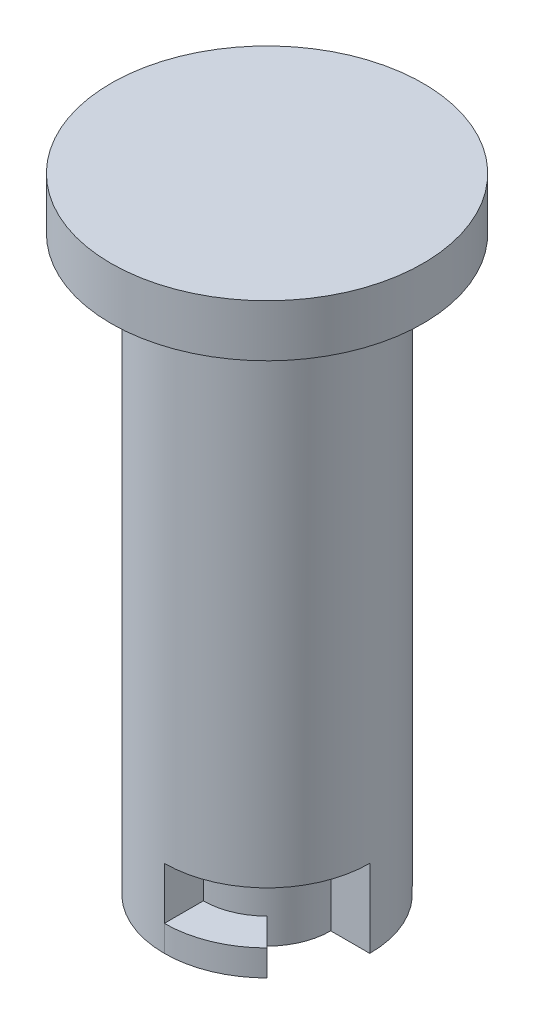
SolidWorks part; units mm, degrees
ref_plane "Alzado" through (0, 0, 0) normal (0, 0, 1) x (1, 0, 0)
ref_plane "Planta" through (0, 0, 0) normal (0, 1, 0) x (1, 0, 0)
ref_plane "Vista lateral" through (0, 0, 0) normal (1, 0, 0) x (0, 0, -1)
sketch "Sketch1" plane through (0, 0, 0) normal (0, 1, 0) x (1, 0, 0)
  circle A0 centre (0, 0) radius 3.95
  dimension "D1" = 7.9
extrude "Boss-Extrude1" add sketch "Sketch1" along normal blind 22
sketch "Sketch2" plane through (0, 22, 0) normal (0, 1, 0) x (1, 0, 0)
  circle A0 centre (0, 0) radius 6
  dimension "D1" = 12
extrude "Boss-Extrude2" add sketch "Sketch2" along normal blind 2
sketch "Sketch3" plane through (0, 0, 0) normal (0, -1, 0) x (1, 0, 0)
  line L0 (0, 3.95) -> (0, 2.45)
  line L1 (1.7324, 1.7324) -> (2.7931, 2.7931)
  line L2 (2.45, 0) -> (3.95, 0)
  arc A0 (0, 3.95) -> (2.7931, 2.7931) centre (0, 0) cw
  circle A1 centre (0, 0) radius 3.95 construction
  arc A2 (0, 2.45) -> (1.7324, 1.7324) centre (0, 0) cw
  arc A3 (2.7931, 2.7931) -> (3.95, 0) centre (0, 0) cw
  arc A4 (1.7324, 1.7324) -> (2.45, 0) centre (0, 0) cw
  circle M4 centre (0, 0) radius 3.95
  dimension "D2" = 45
  dimension "D4" = 45
  dimension "D1" = 1.5
  dimension "D3" = 1.5
extrude "Cut-Extrude1" cut sketch "Sketch3" against normal blind 2 from offset 1 contours L0 A2 L1 M4 region at (1.2152, 0, 2.9338) offset against normal yes
extrude "Cut-Extrude2" cut sketch "Sketch3<3>" against normal blind 3 contours L1 A4 L2 M4 region at (2.9338, 0, 1.2152)
sketch "Sketch3<3>" plane through (0, 0, 0) normal (0, -1, 0) x (1, 0, 0) same geometry as "Sketch3"
